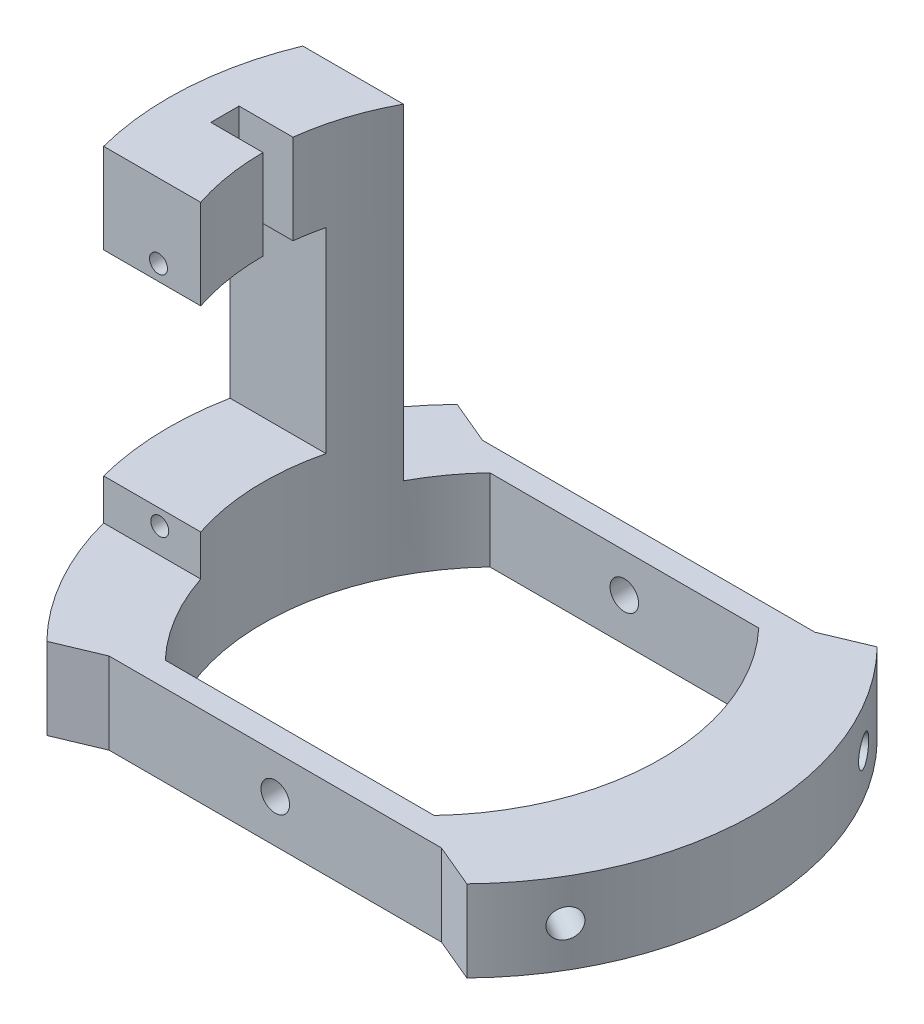
SolidWorks part; units mm, degrees
ref_plane "Front Plane" through (0, 0, 0) normal (0, 0, 1) x (1, 0, 0)
ref_plane "Top Plane" through (0, 0, 0) normal (0, 1, 0) x (1, 0, 0)
ref_plane "Right Plane" through (0, 0, 0) normal (1, 0, 0) x (0, 0, -1)
sketch "Sketch1" plane through (0, 0, 0) normal (0, 1, 0) x (1, 0, 0)
  line L1 (20.3699, -22.9) -> (25.7519, -25.1563)
  line L2 (0, 39.8307) -> (0, -48.2828) construction
  line L3 (-45.5989, 0) -> (54.9461, 0) construction
  line L5 (20.3699, 22.9) -> (25.7519, 25.1563)
  line L6 (-20.3699, -22.9) -> (-25.7519, -25.1563)
  line L7 (-20.3699, 22.9) -> (-25.7519, 25.1563)
  line L8 (-20.3699, -22.9) -> (20.3699, -22.9)
  line L9 (-20.3699, 22.9) -> (20.3699, 22.9)
  line L10 (-16.4881, 19.9) -> (16.4881, 19.9)
  line L11 (-16.4881, -19.9) -> (16.4881, -19.9)
  line L12 (-34.8287, -9.1083) -> (-22.9286, -9.1083)
  line L13 (-33.2722, 13.7463) -> (-20.9304, 13.7463)
  arc A0 (-25.7519, 25.1563) -> (-25.7519, -25.1563) centre (0, 0) ccw
  arc A2 (-16.4881, -19.9) -> (-16.4881, 19.9) centre (4.5948, 0) cw
  arc A3 (16.4881, 19.9) -> (16.4881, -19.9) centre (-4.5948, 0) cw
  arc A4 (25.7519, -25.1563) -> (25.7519, 25.1563) centre (0, 0) ccw
  point P15 (0, -20.5)
  point P17 (0, 20.5)
  dimension "D1" = 72
  dimension "D2" = 3
  dimension "D3" = 3
  dimension "D4" = 39.8
extrude "Boss-Extrude1" add sketch "Sketch1" along normal blind 10 contours L1 A4 L5 L9 L7 A0 L13 A2 L10 A3 L11 L12 L6 L8 region at (0, 0, 22.0312)
extrude "Boss-Extrude3" add sketch "Sketch1<5>" along normal blind 50 contours L12 A2 L13 A0 region at (-29.4038, 0, -2.3846)
sketch "Sketch1<5>" plane through (0, 0, 0) normal (0, 1, 0) x (1, 0, 0) same geometry as "Sketch1"
sketch "Sketch3" plane through (0, 0, 9.1083) normal (0, 0, 1) x (1, 0, 0)
  line L0 (-22.9286, 50) -> (-22.9286, 10) construction
  line L1 (-22.9286, 39) -> (-41.5881, 39)
  line L2 (-22.9286, 39) -> (-22.9286, 15)
  line L3 (-22.9286, 15) -> (-41.5881, 15)
  line L4 (-41.5881, 39) -> (-41.5881, 15)
  line L7 (-34.8287, 10) -> (-22.9286, 10) construction
  dimension "D1" = 24
  dimension "D2" = 5
extrude "Cut-Extrude2" cut sketch "Sketch3" against normal blind 16
sketch "Sketch4" plane through (0, 50, 0) normal (0, 1, 0) x (1, 0, 0)
  line L10 (-30.7989, 3.465) -> (-23.7919, 3.465)
  line L11 (-30.7989, 3.465) -> (-30.7989, 0)
  line L12 (-30.7989, 0) -> (-23.7919, 0)
  line L13 (-23.7919, 3.465) -> (-23.7919, 0)
extrude "Cut-Extrude4" cut sketch "Sketch4" against normal blind 11
sketch "Sketch6" plane through (0, 0, -22.9) normal (0, 0, -1) x (-1, 0, 0)
  line L0 (20.3699, 10) -> (-20.3699, 10) construction
  circle A0 centre (0, 5.25) radius 1.75
  dimension "D1" = 3.5
  dimension "D2" = 4.75
extrude "Cut-Extrude5" cut sketch "Sketch6" against normal blind 50
sketch "Sketch7" plane through (0, 0, 9.1083) normal (0, 0, 1) x (1, 0, 0)
  circle A0 centre (-28.1039, 40.9129) radius 1.1
extrude "Cut-Extrude6" cut sketch "Sketch7" against normal blind 10
sketch "Sketch8" plane through (0, 0, 9.1083) normal (0, 0, 1) x (1, 0, 0)
  circle A0 centre (-27.9449, 13.1133) radius 1.1
extrude "Cut-Extrude7" cut sketch "Sketch8" against normal blind 10
sketch "Sketch11" plane through (0, 10, 0) normal (0, 1, 0) x (1, 0, 0)
  line L0 (0, 0) -> (25.7519, -25.1563) construction
  line L1 (0, 0) -> (30.9995, -18.3039) construction
  line L2 (0, 0) -> (25.7519, 25.1563) construction
  line L3 (0, 0) -> (30.9995, 18.3039) construction
  line L4 (0, -27.5) -> (0, 27.5) construction
  line L5 (0, 0) -> (-25.7519, 25.1563) construction
  line L6 (0, 0) -> (-30.9995, 18.3039) construction
  line L7 (0, 0) -> (-30.9995, -18.3039) construction
  line L8 (0, 0) -> (-25.7519, -25.1563) construction
  arc A0 (25.7519, -25.1563) -> (25.7519, 25.1563) centre (0, 0) ccw construction
ref_plane "Plane1" through (30.9995, 10, 18.3039) normal (0.8611, 0, 0.5084) x (0.5084, 0, -0.8611)
sketch "Sketch12" plane through (30.9995, 10, 18.3039) normal (0.8611, 0, 0.5084) x (0.5084, 0, -0.8611)
  line L0 (34.7553, 0) -> (-8.5686, 0) construction
  circle A0 centre (0, -5) radius 1.75
  dimension "D1" = 3.5
  dimension "D2" = 5
extrude "Cut-Extrude11" cut sketch "Sketch12" against normal blind 6
ref_plane "Plane2" through (30.9995, 10, -18.3039) normal (0.8611, 0, -0.5084) x (-0.5084, 0, -0.8611)
sketch "Sketch13" plane through (30.9995, 10, -18.3039) normal (0.8611, 0, -0.5084) x (-0.5084, 0, -0.8611)
  line L0 (8.5686, 0) -> (-34.7553, 0) construction
  circle A0 centre (0, -5) radius 1.75
  dimension "D1" = 3.5
  dimension "D2" = 5
extrude "Cut-Extrude12" cut sketch "Sketch13" against normal blind 6
ref_plane "Plane3" through (-30.9995, 10, 18.3039) normal (-0.8611, 0, 0.5084) x (0.5084, 0, 0.8611)
sketch "Sketch15" plane through (-30.9995, 10, 18.3039) normal (-0.8611, 0, 0.5084) x (0.5084, 0, 0.8611)
  line L0 (8.5686, 0) -> (-9.8652, 0) construction
  circle A0 centre (0, -5) radius 1.75
  dimension "D1" = 3.5
  dimension "D2" = 5
extrude "Cut-Extrude13" cut sketch "Sketch15" against normal blind 6
ref_plane "Plane4" through (-30.9995, 10, -18.3039) normal (-0.8611, 0, -0.5084) x (-0.5084, 0, 0.8611)
sketch "Sketch16" plane through (-30.9995, 10, -18.3039) normal (-0.8611, 0, -0.5084) x (-0.5084, 0, 0.8611)
  line L0 (5.0801, 0) -> (-8.5686, 0) construction
  circle A0 centre (0, -5) radius 1.75
  dimension "D1" = 3.5
  dimension "D2" = 5
extrude "Cut-Extrude14" cut sketch "Sketch16" against normal blind 6
